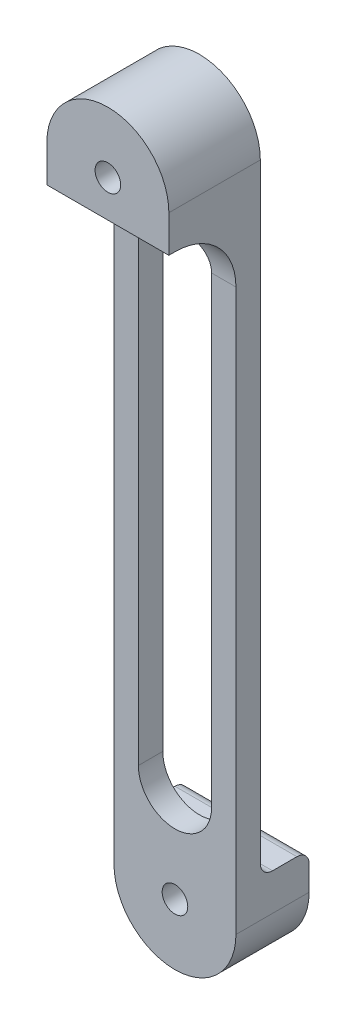
SolidWorks part; units mm, degrees
material "PLA"
ref_plane "Alzado" through (0, 0, 0) normal (0, 0, 1) x (1, 0, 0)
ref_plane "Planta" through (0, 0, 0) normal (0, 1, 0) x (1, 0, 0)
ref_plane "Vista lateral" through (0, 0, 0) normal (1, 0, 0) x (0, 0, -1)
sketch "Croquis1" plane through (0, 0, 0) normal (0, 0, 1) x (1, 0, 0)
  line L0 (0, 54) -> (0, -54) construction
  line L1 (10, 54) -> (10, -54)
  line L2 (-10, 54) -> (-10, -54)
  line L3 (0, 38) -> (0, -38) construction
  line L4 (6, 38) -> (6, -38)
  line L5 (-6, 38) -> (-6, -38)
  line L6 (-10, -47.95) -> (10, -47.95)
  line L7 (0, 51.9) -> (0, 44) construction
  line L8 (-10, 47.95) -> (10, 47.95)
  line L9 (0, -51.9) -> (0, -44) construction
  arc A0 (10, 54) -> (-10, 54) centre (0, 54) ccw
  arc A1 (-10, -54) -> (10, -54) centre (0, -54) ccw
  circle A2 centre (0, 54) radius 2.1
  circle A3 centre (0, -54) radius 2.1
  arc A4 (6, 38) -> (-6, 38) centre (0, 38) ccw
  arc A5 (-6, -38) -> (6, -38) centre (0, -38) ccw
  point P2 (0, 0)
  point P14 (0, 0)
  point P23 (0, 47.95)
  point P28 (0, -47.95)
  dimension "D1" = 4.2
  dimension "D2" = 20
  dimension "D3" = 108
  dimension "D4" = 4
  dimension "D5" = 16
extrude "Saliente-Extruir1" add sketch "Croquis1" along normal blind 4 contours L1 A0 L2 L8 A2 | L2 A1 L1 L8 A5 L5 A4 L4 A3 | L2 A1 L1 A0 | A3 | L5 A5 L4 A4 | A2 region at (9.7436, 50.975, 0) region at (9.0204, 0, 0)
extrude "Saliente-Extruir2" add sketch "Croquis1<5>" against normal blind 8 contours L2 A1 L1 L6 A3 region at (9.7436, -50.975, 0)
sketch "Croquis1<5>" plane through (0, 0, 0) normal (0, 0, 1) x (1, 0, 0) same geometry as "Croquis1"
fillet "Redondeo2" radius 2 2 edges at (0, -47.95, -8) (0, -47.95, 0)
extrude "Saliente-Extruir3" add sketch "Croquis1<6>" along normal blind 15 contours L1 A0 L2 L8 A2 region at (9.7436, 50.975, 0)
sketch "Croquis1<6>" plane through (0, 0, 0) normal (0, 0, 1) x (1, 0, 0) same geometry as "Croquis1"
fillet "Redondeo1" radius 10 1 edges at (0, 47.95, 4)
